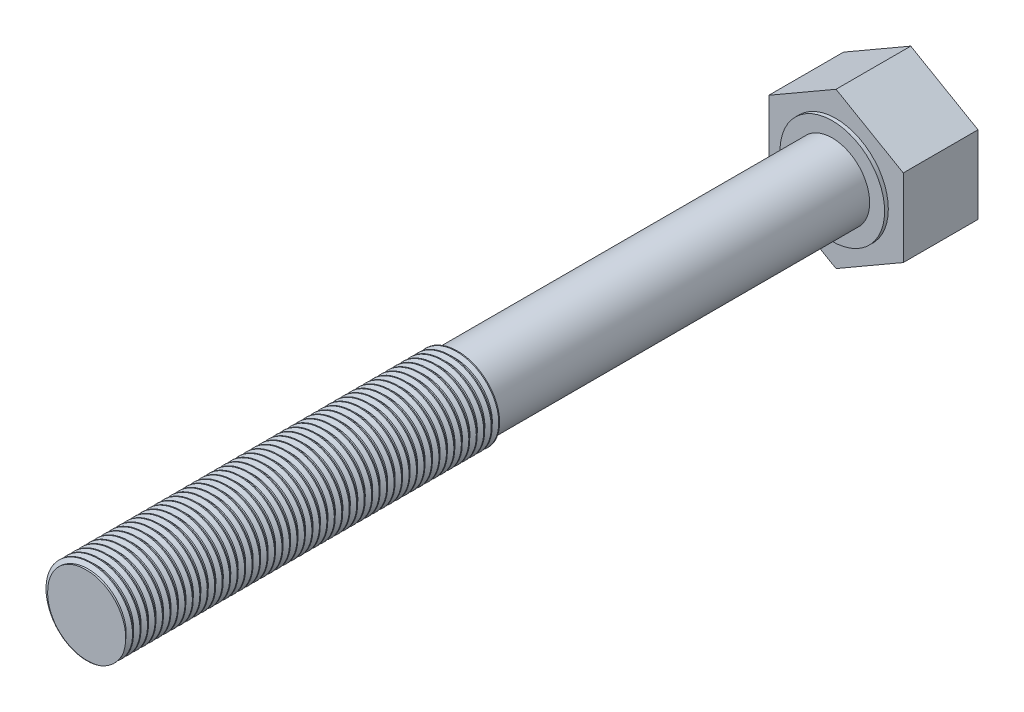
SolidWorks part; units mm, degrees
material "Cast Stainless Steel"
ref_plane "Front Plane" through (0, 0, 0) normal (0, 0, 1) x (1, 0, 0)
ref_plane "Top Plane" through (0, 0, 0) normal (0, 1, 0) x (1, 0, 0)
ref_plane "Right Plane" through (0, 0, 0) normal (1, 0, 0) x (0, 0, -1)
sketch "Sketch2" plane through (0, 0, 0) normal (0, 0, 1) x (1, 0, 0)
  line L1 (0, 5.1962) -> (-4.5, 2.5981)
  line L2 (-4.5, 2.5981) -> (-4.5, -2.5981)
  line L3 (-4.5, -2.5981) -> (0, -5.1962)
  line L4 (0, -5.1962) -> (4.5, -2.5981)
  line L5 (4.5, -2.5981) -> (4.5, 2.5981)
  line L6 (4.5, 2.5981) -> (0, 5.1962)
  circle A0 centre (0, 0) radius 4.5 construction
  dimension "D1" = 9
extrude "Boss-Extrude2" add sketch "Sketch2" against normal blind 5 contours L1 L2 L3 L4 L5 L6
sketch "Sketch3" plane through (0, 0, 0) normal (0, 0, 1) x (1, 0, 0)
  circle A0 centre (0, 0) radius 3.5
  dimension "D1" = 7
extrude "Boss-Extrude3" add sketch "Sketch3" along normal blind 0.25
sketch "Sketch4" plane through (0, 0, 0.25) normal (0, 0, 1) x (1, 0, 0)
  circle A0 centre (0, 0) radius 2.5
  dimension "D1" = 5
extrude "Boss-Extrude4" add sketch "Sketch4" along normal blind 50
thread "Thread1" pitch 0.5 method extrude profile "Thread Profile2" start angle 0, offset 5, length 30, pitch 0.5, diameter 5
ref_plane "Plane2" through (-2.5, 0, 55.25) normal (0, -1, 0) x (-1, 0, 0)
sketch "Thread Profile2" plane through (-2.5, 0, 55.25) normal (0, -1, 0) x (-1, 0, 0)
  line L0 (0, 0) -> (0, 0.5) construction
  line L1 (0, 0) -> (0.2706, 0.1562)
  line L2 (0.2706, 0.1562) -> (0.2706, 0.2187)
  line L3 (0.2706, 0.2187) -> (0, 0.375)
  line L4 (0.2706, 0.1875) -> (0, 0.1875) construction
  line L11 (0, 0) -> (0, 0.375)
  point P2 (0, 0)
  dimension "Pitch" = 0.5
  dimension "Profile_Angle" = 60
  dimension "Profile_Land" = 0.0625
  dimension "Profile_Height" = 0.2706
sketch "Sketch12" plane through (0, 0, 50.25) normal (0, 0, 1) x (1, 0, 0)
  circle A0 centre (0, 0) radius 5
  dimension "D1" = 10
extrude "Cut-Extrude1" cut sketch "Sketch12" along normal blind 20
